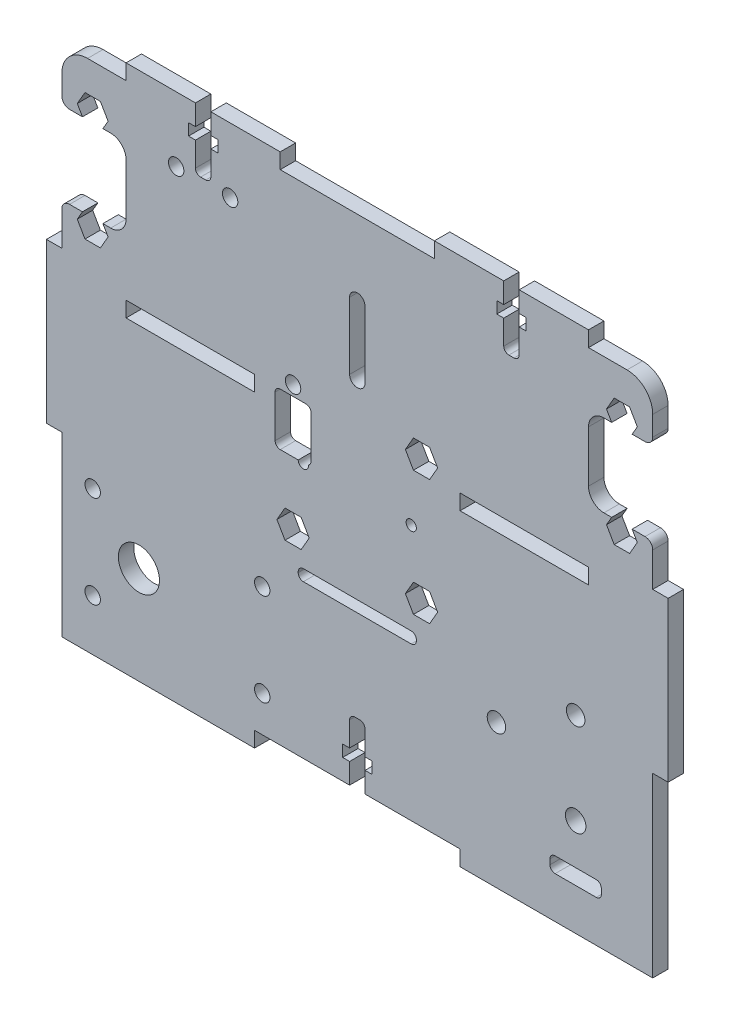
SolidWorks part; units mm, degrees
other "Marcação1"
sketch "Esboço7" plane through (-68, 31.5, 3) normal (-0.6758, 0.2828, 0.6807) x (0.7271, 0.1043, 0.6785)
sketch "Esboço8" plane through (-68, 31.5, 3) normal (-0.6758, 0.2828, 0.6807) x (0.7271, 0.1043, 0.6785)
sketch "Esboço9" plane through (-68, 31.5, 3) normal (-0.6758, 0.2828, 0.6807) x (0.7271, 0.1043, 0.6785)
sketch "Esboço10" plane through (-68, 31.5, 3) normal (-0.6758, 0.2828, 0.6807) x (0.7271, 0.1043, 0.6785)
sketch "Esboço11" plane through (-68, 36.25, 3) normal (-0.6758, 0.2828, 0.6807) x (0.7271, 0.1043, 0.6785)
sketch "Esboço13" plane through (-68, 36.25, 3) normal (-0.6758, 0.2828, 0.6807) x (0.7271, 0.1043, 0.6785)
sketch "Esboço15" plane through (-68, 36.25, 3) normal (-0.6758, 0.2828, 0.6807) x (0.7271, 0.1043, 0.6785)
sketch "Esboço19" plane through (-68, 66.25, 3) normal (-0.6758, 0.2828, 0.6807) x (0.7271, 0.1043, 0.6785)
sketch "Esboço22" plane through (-68, 95.5577, 3) normal (-0.6758, 0.2828, 0.6807) x (0.7271, 0.1043, 0.6785)
sketch "Sketch16" plane through (-60.5, 53, 1.5) normal (-0.6758, 0.2828, 0.6807) x (0.7271, 0.1043, 0.6785)
sketch "Sketch18" plane through (-60.5, 53, 1.5) normal (-0.6758, 0.2828, 0.6807) x (0.7271, 0.1043, 0.6785)
sketch "Sketch19" plane through (-60.5, 53, 1.5) normal (-0.6758, 0.2828, 0.6807) x (0.7271, 0.1043, 0.6785)
sketch "Sketch20" plane through (-60.5, 53, 1.5) normal (-0.6758, 0.2828, 0.6807) x (0.7271, 0.1043, 0.6785)
sketch "Sketch21" plane through (-60.5, 53, 1.5) normal (-0.6758, 0.2828, 0.6807) x (0.7271, 0.1043, 0.6785)
material "Acrylic (Medium-high impact)"
ref_plane "Plano frontal" through (0, 0, 0) normal (0, 0, 1) x (1, 0, 0)
ref_plane "Plano superior" through (0, 0, 0) normal (0, 1, 0) x (1, 0, 0)
ref_plane "Plano direito" through (0, 0, 0) normal (1, 0, 0) x (0, 0, -1)
sketch "Esboço1" plane through (0, 0, 0) normal (0, 0, 1) x (1, 0, 0)
  line L6 (57.5, -50) -> (-57.5, -50)
  line L8 (57.5, -50) -> (57.5, 50)
  line L9 (57.5, 50) -> (-57.5, 50)
  line L10 (-57.5, -50) -> (-57.5, 50)
  line L11 (57.5, -50) -> (-57.5, 50) construction
  line L12 (57.5, 50) -> (-57.5, -50) construction
  point P0 (0, 0)
  dimension "D1" = 100
  dimension "D2" = 115
extrude "Ressalto-extrusão1" add sketch "Esboço1" along normal mid plane 3
sketch "Esboço2" plane through (0, 0, 1.5) normal (0, 0, 1) x (1, 0, 0)
  line L1 (-20, -50) -> (20, -50)
  line L2 (-20, -50) -> (-20, -47)
  line L3 (-20, -47) -> (20, -47)
  line L4 (20, -50) -> (20, -47)
  line L6 (-57.5, -50) -> (57.5, -50) construction
  line L15 (57.5, 50) -> (-57.5, 50) construction
  line L25 (-45, 13) -> (-20, 13)
  line L26 (-45, 13) -> (-45, 10)
  line L29 (-45, 10) -> (-20, 10)
  line L30 (-20, 13) -> (-20, 10)
  line L31 (0, -1.65) -> (0, 1.65) construction
  line L32 (20, 13) -> (20, 10)
  line L33 (45, 10) -> (20, 10)
  line L34 (45, 13) -> (45, 10)
  line L35 (45, 13) -> (20, 13)
  point P6 (0, -47)
  dimension "D4" = 25
  dimension "D3" = 3
  dimension "D1" = 37
  dimension "D2" = 40
  dimension "D5" = 40
extrude "Corte-extrusão1" cut sketch "Esboço2" against normal through all
sketch "Sketch9" plane through (0, 0, 0) normal (0, 0, 1) x (1, 0, 0)
  line L0 (20, -47) -> (-20, -47) construction
  line L1 (-1.5, -47) -> (1.5, -47)
  line L2 (-1.5, -47) -> (-1.5, -43)
  line L3 (-0.5, -35) -> (0.5, -35)
  line L4 (1.5, -47) -> (1.5, -43)
  line L5 (1.5, -40.73) -> (2.85, -40.73)
  line L6 (-2.85, -40.73) -> (-1.5, -40.73)
  line L7 (-2.85, -40.73) -> (-2.85, -43)
  line L8 (-2.85, -43) -> (-1.5, -43)
  line L9 (2.85, -40.73) -> (2.85, -43)
  line L10 (-1.5, -40.73) -> (-1.5, -36)
  line L11 (1.5, -43) -> (2.85, -43)
  line L12 (1.5, -40.73) -> (1.5, -36)
  arc A0 (0.5, -35) -> (1.5, -36) centre (0.5, -36) cw
  arc A1 (-1.5, -36) -> (-0.5, -35) centre (-0.5, -36) cw
  point P6 (0, -35)
  point P18 (1.5, -35)
  point P21 (-1.5, -35)
  dimension "D7" = 1
  dimension "D1" = 3
  dimension "D2" = 12
  dimension "D3" = 2.27
  dimension "D4" = 1.35
  dimension "D5" = 1.35
  dimension "D6" = 4
extrude "Cut-Extrude12" cut sketch "Sketch9" against normal through all both and the other way through all
sketch "Esboço3" plane through (0, 0, 1.5) normal (0, 0, 1) x (1, 0, 0)
  line L0 (57.5, -50) -> (57.5, 50) construction
  line L1 (57.5, 15.5) -> (60.5, 15.5)
  line L2 (57.5, 15.5) -> (57.5, -15.5)
  line L3 (57.5, -15.5) -> (60.5, -15.5)
  line L4 (60.5, 15.5) -> (60.5, -15.5)
  line L5 (0, -1.65) -> (0, 1.65) construction
  line L6 (-57.5, -15.5) -> (-60.5, -15.5)
  line L7 (-57.5, 15.5) -> (-60.5, 15.5)
  line L8 (-57.5, 15.5) -> (-57.5, -15.5)
  line L9 (-60.5, 15.5) -> (-60.5, -15.5)
  line L15 (57.5, 50) -> (-57.5, 50) construction
  line L16 (-45, 50) -> (-15, 50)
  line L17 (-45, 50) -> (-45, 53)
  line L18 (-45, 53) -> (-15, 53)
  line L19 (-15, 50) -> (-15, 53)
  line L20 (15, 50) -> (15, 53)
  line L21 (45, 53) -> (15, 53)
  line L22 (45, 50) -> (45, 53)
  line L23 (45, 50) -> (15, 50)
  line L24 (-57.5, 50) -> (-57.5, -50) construction
  point P6 (57.5, 0)
  dimension "D1" = 3
  dimension "D2" = 31
  dimension "D3" = 30
  dimension "D4" = 15
  dimension "D5" = 12.5
extrude "Ressalto-extrusão2" add sketch "Esboço3" against normal through all
sketch "Esboço30" plane through (0, 0, -1.5) normal (0, 0, -1) x (-1, 0, 0)
  line L2 (57.5, -15.5) -> (57.5, -50) construction
  line L6 (57.5, -50) -> (20, -50) construction
  circle A1 centre (42.5, -31) radius 4
  dimension "D1" = 15
  dimension "D2" = 19
  dimension "D3" = 8
extrude "Corte-extrusão11" cut sketch "Esboço30" against normal through all both and the other way through all
sketch "Esboço4" plane through (0, 0, 1.5) normal (0, 0, 1) x (1, 0, 0)
  line L0 (57.5, -50) -> (57.5, -15.5) construction
  line L76 (-46.5, -31) -> (-38.5, -31) construction
  circle A11 centre (42.5, -31) radius 2
  circle A14 centre (-42.5, -31) radius 4 construction
  dimension "D1" = 15
  dimension "D2" = 4
extrude "Corte-extrusão2" cut sketch "Esboço4" against normal through all
sketch "Esboço31" plane through (0, 0, -1.5) normal (0, 0, -1) x (-1, 0, 0)
  line L1 (57.5, -15.5) -> (57.5, -50) construction
  line L2 (46.5, -31) -> (38.5, -31) construction
  circle A4 centre (51.5, -22) radius 1.5
  circle A5 centre (51.5, -40) radius 1.5
  circle A6 centre (42.5, -31) radius 4 construction
  circle A7 centre (18.5, -22) radius 1.5
  circle A8 centre (18.5, -40) radius 1.5
  dimension "D1" = 3
  dimension "D3" = 6
  dimension "D4" = 18
  dimension "D5" = 33
extrude "Corte-extrusão12" cut sketch "Esboço31" against normal through all both and the other way through all
sketch "Sketch8" plane through (0, 0, -1.5) normal (0, 0, -1) x (-1, 0, 0)
  line L31 (-57.5, 39.6519) -> (-53.4896, 39.6519)
  line L32 (-58, 31.6519) -> (-58, 23.6519) construction
  line L33 (-57.5, 23.6519) -> (-53.4896, 23.6519)
  line L34 (-45, 36.6519) -> (-45, 26.6519)
  line L35 (-57.5, 15.5) -> (-57.5, 50) construction
  line L37 (-48.5, 41.4019) -> (-50, 44)
  line L38 (-50, 44) -> (-53, 44)
  line L39 (-53, 44) -> (-54.5, 41.4019)
  line L40 (-54.5, 41.4019) -> (-53.4896, 39.6519)
  line L42 (-49.5104, 39.6519) -> (-48.5, 41.4019)
  line L43 (-49.5104, 39.6519) -> (-48, 39.6519)
  line L45 (-51.7693, 38.8038) -> (-50.2755, 38.8038) [skipped]
  line L46 (-58, 31.6519) -> (-45, 31.6519) construction
  line L48 (-49.5104, 23.6519) -> (-48.5, 21.9019)
  line L49 (-54.5, 21.9019) -> (-53.4896, 23.6519)
  line L50 (-53, 19.3038) -> (-54.5, 21.9019)
  line L51 (-50, 19.3038) -> (-53, 19.3038)
  line L52 (-48.5, 21.9019) -> (-50, 19.3038)
  line L53 (-49.5104, 23.6519) -> (-48, 23.6519)
  line L54 (-57.5, 23.6519) -> (-57.5, 39.6519)
  line L55 (-58, 39.6519) -> (-57.5, 39.6519) construction
  line L56 (-58, 39.6519) -> (-58, 31.6519) construction
  line L57 (-58, 23.6519) -> (-57.5, 23.6519) construction
  line L58 (-57.5, 50) -> (-45, 50) construction
  line L59 (0, 1.65) -> (0, -1.65) construction
  line L60 (58, 23.6519) -> (57.5, 23.6519) construction
  line L61 (58, 39.6519) -> (58, 31.6519) construction
  line L62 (58, 39.6519) -> (57.5, 39.6519) construction
  line L63 (58, 31.6519) -> (45, 31.6519) construction
  line L64 (58, 31.6519) -> (58, 23.6519) construction
  line L65 (57.5, 23.6519) -> (57.5, 39.6519)
  line L66 (49.5104, 23.6519) -> (48, 23.6519)
  line L67 (48.5, 21.9019) -> (50, 19.3038)
  line L68 (50, 19.3038) -> (53, 19.3038)
  line L69 (53, 19.3038) -> (54.5, 21.9019)
  line L70 (54.5, 21.9019) -> (53.4896, 23.6519)
  line L71 (49.5104, 23.6519) -> (48.5, 21.9019)
  line L72 (49.5104, 39.6519) -> (48, 39.6519)
  line L73 (49.5104, 39.6519) -> (48.5, 41.4019)
  line L74 (54.5, 41.4019) -> (53.4896, 39.6519)
  line L75 (53, 44) -> (54.5, 41.4019)
  line L76 (50, 44) -> (53, 44)
  line L77 (48.5, 41.4019) -> (50, 44)
  line L78 (45, 36.6519) -> (45, 26.6519)
  line L79 (57.5, 23.6519) -> (53.4896, 23.6519)
  line L80 (57.5, 39.6519) -> (53.4896, 39.6519)
  arc A10 (-48, 23.6519) -> (-45, 26.6519) centre (-48, 26.6519) ccw
  arc A12 (-48, 39.6519) -> (-45, 36.6519) centre (-48, 36.6519) cw
  arc A14 (-49.25, 40.1029) -> (-53.75, 40.1029) centre (-51.5, 41.4019) ccw construction
  arc A15 (-49.25, 23.201) -> (-53.75, 23.201) centre (-51.5, 21.9019) cw construction
  arc A16 (49.25, 23.201) -> (53.75, 23.201) centre (51.5, 21.9019) ccw construction
  arc A17 (49.25, 40.1029) -> (53.75, 40.1029) centre (51.5, 41.4019) cw construction
  arc A18 (48, 39.6519) -> (45, 36.6519) centre (48, 36.6519) ccw
  arc A19 (48, 23.6519) -> (45, 26.6519) centre (48, 26.6519) cw
  point P9 (-45, 23.6519)
  point P14 (-45, 39.6519)
  point P17 (-58, 39.6519)
  point P38 (-51.5, 31.6519)
  point P73 (45, 39.6519)
  point P74 (45, 23.6519)
  dimension "D1" = 13
  dimension "D2" = 3
  dimension "D5" = 3
  dimension "D6" = 3
  dimension "D3" = 16
  dimension "D7" = 19.5
  dimension "D8" = 6
sketch "Sketch11" plane through (0, 0, 0) normal (0, 0, 1) x (1, 0, 0)
  line L0 (45, 53) -> (15, 53) construction
  line L1 (28.5, 53) -> (31.5, 53)
  line L2 (28.5, 53) -> (28.5, 49)
  line L3 (29.5, 41) -> (30.5, 41)
  line L4 (31.5, 53) -> (31.5, 49)
  line L5 (15, 53) -> (15, 50) construction
  line L6 (28.5, 46.73) -> (28.5, 42)
  line L7 (27.15, 49) -> (28.5, 49)
  line L8 (27.15, 49) -> (27.15, 46.73)
  line L9 (27.15, 46.73) -> (28.5, 46.73)
  line L10 (32.85, 49) -> (32.85, 46.73)
  line L11 (31.5, 49) -> (32.85, 49)
  line L12 (31.5, 46.73) -> (31.5, 42)
  line L13 (31.5, 46.73) -> (32.85, 46.73)
  line L27 (0, -1.65) -> (0, 1.65) construction
  line L28 (-31.5, 46.73) -> (-32.85, 46.73)
  line L29 (-31.5, 46.73) -> (-31.5, 42)
  line L30 (-31.5, 49) -> (-32.85, 49)
  line L31 (-32.85, 49) -> (-32.85, 46.73)
  line L32 (-27.15, 46.73) -> (-28.5, 46.73)
  line L33 (-27.15, 49) -> (-27.15, 46.73)
  line L34 (-27.15, 49) -> (-28.5, 49)
  line L35 (-28.5, 46.73) -> (-28.5, 42)
  line L36 (-31.5, 53) -> (-31.5, 49)
  line L37 (-29.5, 41) -> (-30.5, 41)
  line L38 (-28.5, 53) -> (-28.5, 49)
  line L39 (-28.5, 53) -> (-31.5, 53)
  arc A0 (30.5, 41) -> (31.5, 42) centre (30.5, 42) ccw
  arc A1 (28.5, 42) -> (29.5, 41) centre (29.5, 42) ccw
  arc A4 (-28.5, 42) -> (-29.5, 41) centre (-29.5, 42) cw
  arc A5 (-30.5, 41) -> (-31.5, 42) centre (-30.5, 42) cw
  point P20 (28.5, 41)
  point P39 (-28.5, 41)
  dimension "D8" = 1
  dimension "D1" = 3
  dimension "D2" = 12
  dimension "D3" = 13.5
  dimension "D4" = 1.35
  dimension "D5" = 2.27
  dimension "D7" = 4
extrude "Cut-Extrude14" cut sketch "Sketch11" against normal through all both and the other way through all
sketch "Sketch13" plane through (0, 0, 0) normal (0, 0, 1) x (1, 0, 0)
  line L18 (-10, 13.0193) -> (-15, 13.0193)
  line L19 (-9, 12.0193) -> (-9, 3.8193)
  line L20 (-10, 2.8193) -> (-15, 2.8193)
  line L21 (-16, 12.0193) -> (-16, 3.8193)
  line L23 (15.64, 15.0193) -> (14.07, 17.7386)
  line L24 (14.07, 17.7386) -> (10.93, 17.7386)
  line L25 (10.93, 17.7386) -> (9.36, 15.0193)
  line L26 (9.36, 15.0193) -> (10.93, 12.3)
  line L27 (10.93, 12.3) -> (14.07, 12.3)
  line L28 (14.07, 12.3) -> (15.64, 15.0193)
  line L30 (15.64, -9.2807) -> (14.07, -6.5614)
  line L31 (14.07, -6.5614) -> (10.93, -6.5614)
  line L32 (10.93, -6.5614) -> (9.36, -9.2807)
  line L33 (9.36, -9.2807) -> (10.93, -12)
  line L34 (10.93, -12) -> (14.07, -12)
  line L35 (14.07, -12) -> (15.64, -9.2807)
  line L38 (-9.36, -9.2807) -> (-10.93, -6.5614)
  line L39 (-10.93, -6.5614) -> (-14.07, -6.5614)
  line L40 (-14.07, -6.5614) -> (-15.64, -9.2807)
  line L41 (-15.64, -9.2807) -> (-14.07, -12)
  line L42 (-14.07, -12) -> (-10.93, -12)
  line L43 (-10.93, -12) -> (-9.36, -9.2807)
  line L45 (-12.5, 15.0193) -> (12.5, 15.0193) construction
  circle A1 centre (12.5, 15.0193) radius 1.5 construction
  circle A2 centre (-12.5, -9.2807) radius 1.5 construction
  circle A3 centre (12.5, -9.2807) radius 1.5 construction
  circle A10 centre (-12.5, 15.0193) radius 1.5
  arc A11 (-15, 2.8193) -> (-16, 3.8193) centre (-15, 3.8193) cw
  arc A12 (-9, 3.8193) -> (-10, 2.8193) centre (-10, 3.8193) cw
  arc A13 (-15, 13.0193) -> (-16, 12.0193) centre (-15, 12.0193) ccw
  arc A14 (-10, 13.0193) -> (-9, 12.0193) centre (-10, 12.0193) cw
  circle A15 centre (12.5, 15.0193) radius 2.7193 construction
  circle A16 centre (12.5, -9.2807) radius 2.7193 construction
  circle A17 centre (-12.5, -9.2807) radius 2.7193 construction
  circle A18 centre (-18.5, -22) radius 1.5 construction
  point P10 (0, 15.0193)
  point P16 (-12.5, 13.0193)
  point P19 (-16, 2.8193)
  point P25 (-16, 13.0193)
  dimension "D1" = 3
  dimension "D3" = 25
  dimension "D2" = 24.3
  dimension "D6" = 0.5
  dimension "D4" = 8.5
  dimension "D9" = 1
  dimension "D10" = 3.14
  dimension "D7" = 10.2
  dimension "D8" = 2
extrude "Cut-Extrude16" cut sketch "Sketch13" against normal through all both and the other way through all
sketch "Esboço34" plane through (0, 0, -1.5) normal (0, 0, -1) x (-1, 0, 0)
  line L0 (-10.93, -12) -> (-14.07, -12) construction
  line L1 (11.5, -16) -> (11.5, -16.2)
  line L2 (10.5, -15) -> (-10.5, -15)
  line L3 (-11.5, -16) -> (-11.5, -16.2)
  line L4 (10.5, -17.2) -> (-10.5, -17.2)
  circle A0 centre (10.5, 2.82) radius 1
  circle A1 centre (-10.5, 2.82) radius 1
  arc A2 (11.5, -16.2) -> (10.5, -17.2) centre (10.5, -16.2) cw
  arc A3 (11.5, -16) -> (10.5, -15) centre (10.5, -16) ccw
  arc A4 (-11.5, -16.2) -> (-10.5, -17.2) centre (-10.5, -16.2) ccw
  arc A5 (-10.5, -15) -> (-11.5, -16) centre (-10.5, -16) ccw
  point P4 (0, -17.2)
  point P21 (11.5, -17.2)
  point P24 (11.5, -15)
  point P29 (-11.5, -15)
  dimension "D1" = 2
  dimension "D2" = 3
  dimension "D3" = 2.82
  dimension "D4" = 21
  dimension "D6" = 10.5
  dimension "D8" = 1
  dimension "D5" = 2.2
  dimension "D7" = 23
extrude "Corte-extrusão13" cut sketch "Esboço34" against normal through all both and the other way through all
sketch "Sketch12" plane through (0, 0, -1.5) normal (0, 0, 1) x (1, 0, 0)
  line L3 (0, 22.2386) -> (0, 35.2386) construction
  line L6 (-1.5, 22.2386) -> (-1.5, 35.2386)
  line L7 (1.5, 22.2386) -> (1.5, 35.2386)
  line L8 (-2, 23.2803) -> (-6, 23.2803)
  line L9 (-2, 22.2386) -> (-6, 22.2386)
  line L10 (-2, 22.2386) -> (-2, 22.7386)
  line L11 (-2, 22.7386) -> (-6, 22.7386)
  line L12 (-6, 22.2386) -> (-6, 22.7386)
  line L13 (-2, 23.2803) -> (-2, 23.7803)
  line L14 (-2, 23.7803) -> (-6, 23.7803)
  line L15 (-6, 23.2803) -> (-6, 23.7803)
  line L16 (-2, 24.322) -> (-6, 24.322)
  line L17 (-2, 24.322) -> (-2, 24.822)
  line L18 (-2, 24.822) -> (-6, 24.822)
  line L19 (-6, 24.322) -> (-6, 24.822)
  line L20 (-2, 25.3636) -> (-6, 25.3636)
  line L21 (-2, 25.3636) -> (-2, 25.8636)
  line L22 (-2, 25.8636) -> (-6, 25.8636)
  line L23 (-6, 25.3636) -> (-6, 25.8636)
  line L24 (-2, 26.4053) -> (-6, 26.4053)
  line L25 (-2, 26.4053) -> (-2, 26.9053)
  line L26 (-2, 26.9053) -> (-6, 26.9053)
  line L27 (-6, 26.4053) -> (-6, 26.9053)
  line L28 (-2, 27.447) -> (-6, 27.447)
  line L29 (-2, 27.447) -> (-2, 27.947)
  line L30 (-2, 27.947) -> (-6, 27.947)
  line L31 (-6, 27.447) -> (-6, 27.947)
  line L32 (-2, 28.4886) -> (-6, 28.4886)
  line L33 (-2, 28.4886) -> (-2, 28.9886)
  line L34 (-2, 28.9886) -> (-6, 28.9886)
  line L35 (-6, 28.4886) -> (-6, 28.9886)
  line L36 (-2, 29.5303) -> (-6, 29.5303)
  line L37 (-2, 29.5303) -> (-2, 30.0303)
  line L38 (-2, 30.0303) -> (-6, 30.0303)
  line L39 (-6, 29.5303) -> (-6, 30.0303)
  line L40 (-2, 30.572) -> (-6, 30.572)
  line L41 (-2, 30.572) -> (-2, 31.072)
  line L42 (-2, 31.072) -> (-6, 31.072)
  line L43 (-6, 30.572) -> (-6, 31.072)
  line L44 (-2, 31.6136) -> (-6, 31.6136)
  line L45 (-2, 31.6136) -> (-2, 32.1136)
  line L46 (-2, 32.1136) -> (-6, 32.1136)
  line L47 (-6, 31.6136) -> (-6, 32.1136)
  line L48 (-2, 32.6553) -> (-6, 32.6553)
  line L49 (-2, 32.6553) -> (-2, 33.1553)
  line L50 (-2, 33.1553) -> (-6, 33.1553)
  line L51 (-6, 32.6553) -> (-6, 33.1553)
  line L52 (-2, 33.697) -> (-6, 33.697)
  line L53 (-2, 33.697) -> (-2, 34.197)
  line L54 (-2, 34.197) -> (-6, 34.197)
  line L55 (-6, 33.697) -> (-6, 34.197)
  line L56 (-2, 34.7386) -> (-6, 34.7386)
  line L57 (-2, 34.7386) -> (-2, 35.2386)
  line L58 (-2, 35.2386) -> (-6, 35.2386)
  line L59 (-6, 34.7386) -> (-6, 35.2386)
  line L66 (14.07, 17.7386) -> (10.93, 17.7386) construction
  circle A1 centre (0, 22.2386) radius 1.5 construction
  arc A4 (-1.5, 22.2386) -> (1.5, 22.2386) centre (0, 22.2386) ccw
  arc A5 (1.5, 35.2386) -> (-1.5, 35.2386) centre (0, 35.2386) ccw
  point P4 (0, 28.7386)
  dimension "D1" = 3
  dimension "D2" = 13
  dimension "D3" = 0.5
  dimension "D4" = 3
  dimension "D5" = 4
  dimension "D6" = 0.5
  dimension "D7" = 13
extrude "Cut-Extrude15" cut sketch "Sketch12" along normal through all contours L7 A5 L6 A4 | A5 L7 A4 L6 region at (0, 28.7386, -1.5)
extrude "Cut-Extrude18" cut sketch "Sketch12<3>" along normal blind 0.1 contours L59 L56 L57 L58 | L55 L52 L53 L54 | L51 L48 L49 L50 | L47 L44 L45 L46 | L39 L36 L37 L38 | L43 L40 L41 L42 | L31 L28 L29 L30 | L35 L32 L33 L34 | L27 L24 L25 L26 | L23 L20 L21 L22 | L19 L16 L17 L18 | L15 L8 L13 L14 | L12 L9 L10 L11 | L56 L59 L58 L57 | L52 L55 L54 L53 | L48 L51 L50 L49 | L44 L47 L46 L45 | L40 L43 L42 L41 | L36 L39 L38 L37 | L32 L35 L34 L33 | L28 L31 L30 L29 | L24 L27 L26 L25 | L20 L23 L22 L21 | L16 L19 L18 L17 | L8 L15 L14 L13 | L9 L12 L11 L10 | L42 L43 L40 L41 | L38 L39 L36 L37 region at (-4, 23.5303, -1.5) region at (-4, 22.4886, -1.5) region at (-4, 24.572, -1.5) region at (-4, 25.6136, -1.5) region at (-4, 26.6553, -1.5) region at (-4, 27.697, -1.5) region at (-4, 28.7386, -1.5) region at (-4, 29.7803, -1.5) region at (-4, 30.822, -1.5) region at (-4, 31.8636, -1.5) region at (-4, 32.9053, -1.5) region at (-4, 33.947, -1.5) region at (-4, 34.9886, -1.5)
sketch "Sketch12<3>" plane through (0, 0, -1.5) normal (0, 0, 1) x (1, 0, 0) same geometry as "Sketch12"
fillet "Fillet1" radius 5 2 edges at (57.5, 50, 0) (-57.5, 50, 0)
sketch "Sketch14" plane through (0, 0, 0) normal (0, 0, 1) x (1, 0, 0)
  line L0 (-30, 42.1706) -> (-30, 58.8294) construction
  line L1 (-45, 53) -> (-15, 53) construction
  line L3 (15, 50) -> (-15, 50) construction
  circle A0 centre (-24.75, 40.4) radius 1.5
  circle A1 centre (-35.25, 40.4) radius 1.5
  point P5 (-30, 53)
  point P7 (-30, 53)
  dimension "D1" = 3
  dimension "D2" = 10.5
  dimension "D3" = 9.6
extrude "Cut-Extrude17" cut sketch "Sketch14" against normal through all both and the other way through all
extrude "Cut-Extrude19" cut sketch "Sketch8" against normal through all both and the other way through all
fillet "Fillet3" radius 1.5 4 edges at (57.5, 23.6519, 0) (57.5, 39.6519, 0) (-57.5, 23.6519, 0) (-57.5, 39.6519, 0)
sketch "Sketch15" plane through (0, 0, 0) normal (0, 0, 1) x (1, 0, 0)
  line L0 (57.5, 15.5) -> (57.5, 22.1519) construction
  line L1 (54.5, 33.7) -> (43, 33.7)
  line L2 (54.5, 33.7) -> (54.5, 30.7)
  line L3 (54.5, 30.7) -> (43, 30.7)
  line L4 (43, 33.7) -> (43, 30.7)
  line L5 (52.5, 50) -> (45, 50) construction
  line L6 (0, -1.65) -> (0, 1.65) construction
  line L7 (-43, 33.7) -> (-43, 30.7)
  line L8 (-54.5, 30.7) -> (-43, 30.7)
  line L9 (-54.5, 33.7) -> (-54.5, 30.7)
  line L10 (-54.5, 33.7) -> (-43, 33.7)
  circle A0 centre (51.25, 41.5) radius 1.5
  circle A2 centre (-46.25, 41.5) radius 1.5
  point P8 (48.75, 33.7)
  point P20 (-48.75, 33.7)
  dimension "D4" = 3
  dimension "D7" = 7
  dimension "D8" = 2.5
  dimension "D1" = 11.5
  dimension "D2" = 3
  dimension "D3" = 3
  dimension "D5" = 7.8
  dimension "D6" = 2.5
extrude "Corte GY-53LDK" [suppressed] cut sketch "Sketch15" against normal through all both and the other way through all
sketch "Sketch17" plane through (0, 0, -1.5) normal (0, 0, -1) x (-1, 0, 0)
  line L0 (-42.5, -43) -> (-42.5, -38) construction
  line L4 (-46.5, -38.9087) -> (-38.5, -38.9087)
  line L5 (-47.5, -39.9087) -> (-47.5, -40.9087)
  line L6 (-46.5, -41.9087) -> (-38.5, -41.9087)
  line L7 (-37.5, -39.9087) -> (-37.5, -40.9087)
  line L8 (-31.917, -38) -> (-53.083, -38) construction
  circle A4 centre (-42.5, -13.2) radius 1.8 construction
  circle A5 centre (-42.5, -31) radius 12 construction
  arc A6 (-47.5, -40.9087) -> (-46.5, -41.9087) centre (-46.5, -40.9087) ccw
  arc A7 (-46.5, -38.9087) -> (-47.5, -39.9087) centre (-46.5, -39.9087) ccw
  arc A8 (-38.5, -38.9087) -> (-37.5, -39.9087) centre (-38.5, -39.9087) cw
  arc A9 (-38.5, -41.9087) -> (-37.5, -40.9087) centre (-38.5, -40.9087) ccw
  circle A10 centre (-42.5, -13.2) radius 1.8
  circle A11 centre (-27.0847, -22.1) radius 1.8 construction
  circle A12 centre (-27.0847, -22.1) radius 1.8
  point P20 (-47.5, -41.9087)
  point P23 (-47.5, -38.9087)
  point P28 (-37.5, -41.9087)
  dimension "D4" = 1
  dimension "D2" = 3
  dimension "D3" = 10
extrude "Cut-Extrude20" cut sketch "Sketch17" against normal through all both and the other way through all
